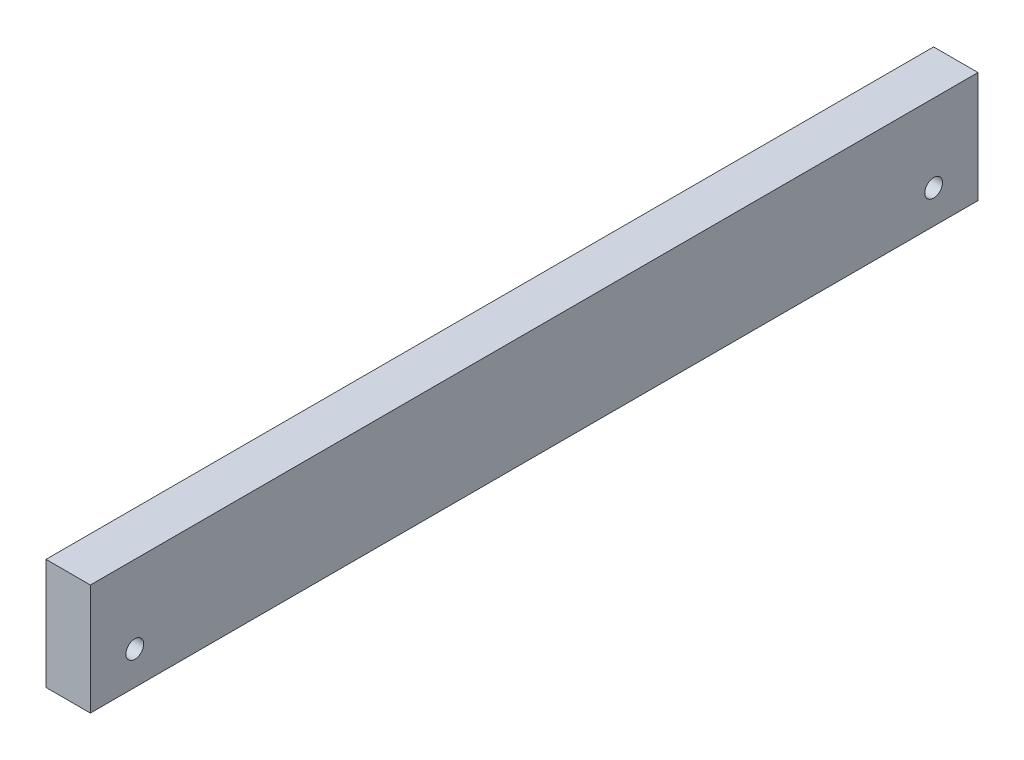
SolidWorks part; units mm, degrees
ref_plane "Front Plane" through (0, 0, 0) normal (0, 0, 1) x (1, 0, 0)
ref_plane "Top Plane" through (0, 0, 0) normal (0, 1, 0) x (1, 0, 0)
ref_plane "Right Plane" through (0, 0, 0) normal (1, 0, 0) x (0, 0, -1)
sketch "Sketch1" plane through (0, 0, 0) normal (0, 0, 1) x (1, 0, 0)
  line L1 (0, 0) -> (20, 0)
  line L2 (0, 0) -> (0, 50)
  line L3 (0, 50) -> (20, 50)
  line L4 (20, 0) -> (20, 50)
  dimension "D1" = 20
  dimension "D2" = 50
extrude "Extrude1" add sketch "Sketch1" along normal blind 400
hole_wizard "Ø8.0 (8) Diameter Hole1" positions "3DSketch1" profile "Sketch2" hole size "Ø8.0" standard "Ansi Metric" end condition through all
sketch3d "3DSketch1"
  line L0 (20, 0, 400) -> (20, 0, 0) construction
  line L1 (20, 0, 0) -> (20, 50, 0) construction
  line L2 (20, 0, 400) -> (20, 50, 400) construction
  point P0 (20, 15, 380)
  point P2 (20, 15, 20)
  dimension "D1" = 15
  dimension "D2" = 15
  dimension "D3" = 20
  dimension "D4" = 20
sketch "Sketch2" plane through (20, 15, 380) normal (0, 1, 0) x (0, 0, -1)
  line L0 (0, 0) -> (0, 20)
  line L1 (0, 20) -> (4, 20)
  line L2 (4, 20) -> (4, 0)
  line L5 (4, 0) -> (0, 0)
  line L11 (0, -6.35) -> (0, 107.95) construction
  dimension "Thru Hole Dia." = 8
  dimension "Thru Hole Depth" = 20
